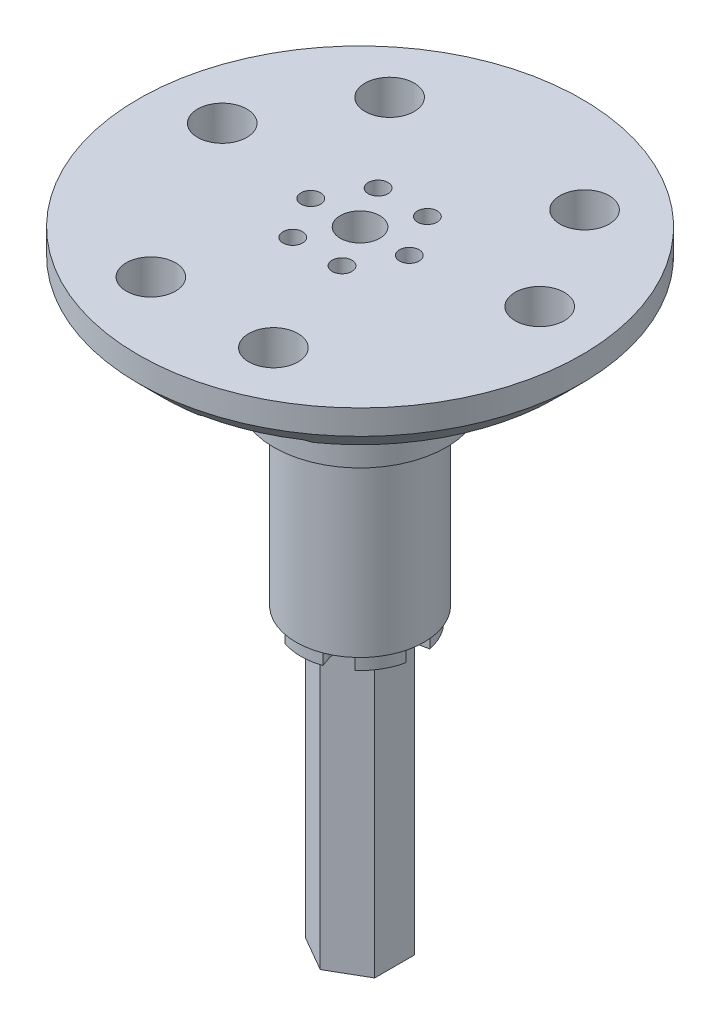
SolidWorks part; units mm, degrees
material "ABS"
ref_plane "Front Plane" through (0, 0, 0) normal (0, 0, 1) x (1, 0, 0)
ref_plane "Top Plane" through (0, 0, 0) normal (0, 1, 0) x (1, 0, 0)
ref_plane "Right Plane" through (0, 0, 0) normal (1, 0, 0) x (0, 0, -1)
sketch "Sketch1" plane through (0, 0, 0) normal (0, 0, 1) x (1, 0, 0)
  line L0 (1.5564, -6.25) -> (1.5564, 63.25)
  line L1 (9.5564, -6.25) -> (9.5564, -3.25)
  line L2 (4.5564, -6.25) -> (1.5564, -6.25)
  line L5 (-2.4436, 63.25) -> (-2.4436, -63.25) construction
  line L11 (42.5564, 63.25) -> (42.5564, 53.25)
  line L15 (42.5564, 53.25) -> (22.5564, 53.25)
  line L16 (1.5564, 63.25) -> (42.5564, 63.25)
  line L20 (17.5564, 48.25) -> (17.5564, 40.25)
  line L21 (15.5564, 41.25) -> (15.5564, 40.25)
  line L22 (16.0564, 41.25) -> (15.5564, 41.25)
  line L23 (15.0564, 42.25) -> (15.0564, 33.25)
  line L24 (15.0564, 33.25) -> (12.5564, 33.25)
  line L25 (10.5564, 31.25) -> (10.5564, -3.25)
  line L36 (9.5564, -6.25) -> (4.5564, -6.25)
  line L40 (15.5564, 40.25) -> (17.5564, 40.25)
  line L42 (10.5564, -3.25) -> (9.5564, -3.25)
  arc A1 (22.5564, 53.25) -> (17.5564, 48.25) centre (22.5564, 48.25) ccw
  arc A2 (16.0564, 41.25) -> (15.0564, 42.25) centre (16.0564, 42.25) ccw
  arc A3 (12.5564, 33.25) -> (10.5564, 31.25) centre (12.5564, 31.25) ccw
revolve "Revolve1" add sketch "Sketch1" angle 360 about L5
sketch "Sketch2" plane through (0, -6.25, 0) normal (0, -1, 0) x (1, 0, 0)
  line L0 (4.5564, 4.0415) -> (4.5564, -4.0415)
  line L1 (-2.4436, 8.0829) -> (4.5564, 4.0415)
  line L2 (-9.4436, 4.0415) -> (-2.4436, 8.0829)
  line L3 (-9.4436, -4.0415) -> (-9.4436, 4.0415)
  line L4 (-2.4436, -8.0829) -> (-9.4436, -4.0415)
  line L5 (4.5564, -4.0415) -> (-2.4436, -8.0829)
  line L6 (-2.4436, 12) -> (-2.4436, -12) construction
  circle A0 centre (-2.4436, 0) radius 4
  circle A1 centre (-2.4436, 0) radius 12 construction
  circle A2 centre (-2.4436, 0) radius 12 construction
extrude "Boss-Extrude1" add sketch "Sketch2" along normal blind 57
sketch "Sketch3" plane through (0, -6.25, 0) normal (0, -1, 0) x (1, 0, 0)
  line L0 (-2.4436, 12) -> (-2.4436, -12) construction
  line L1 (-9.067, 7.4921) -> (-10.3917, 8.9905)
  line L2 (-5.6203, 9.482) -> (-6.2556, 11.3784)
  line L3 (4.1797, 7.4921) -> (5.5044, 8.9905)
  line L4 (0.733, 9.482) -> (1.3683, 11.3784)
  line L5 (7.3564, -1.99) -> (9.3164, -2.388)
  line L6 (7.3564, 1.99) -> (9.3164, 2.388)
  line L7 (0.733, -9.482) -> (1.3683, -11.3784)
  line L8 (4.1797, -7.4921) -> (5.5044, -8.9905)
  line L9 (-9.067, -7.4921) -> (-10.3917, -8.9905)
  line L10 (-5.6203, -9.482) -> (-6.2556, -11.3784)
  line L11 (-12.2436, 1.99) -> (-14.2036, 2.388)
  line L12 (-12.2436, -1.99) -> (-14.2036, -2.388)
  arc A1 (0.733, 9.482) -> (4.1797, 7.4921) centre (2.5564, 8.6603) ccw
  arc A2 (-12.2436, -1.99) -> (-12.2436, 1.99) centre (-12.4436, 0) ccw
  arc A3 (4.1797, -7.4921) -> (0.733, -9.482) centre (2.5564, -8.6603) ccw
  arc A4 (-9.067, 7.4921) -> (-5.6203, 9.482) centre (-7.4436, 8.6603) ccw
  arc A5 (-5.6203, -9.482) -> (-9.067, -7.4921) centre (-7.4436, -8.6603) ccw
  arc A6 (7.3564, 1.99) -> (7.3564, -1.99) centre (7.5564, 0) ccw
  circle A8 centre (-2.4436, 0) radius 12 construction
  circle A9 centre (-2.4436, 0) radius 12 construction
  arc A11 (-6.2556, 11.3784) -> (-10.3917, 8.9905) centre (-2.4436, 0) ccw
  arc A12 (-10.3917, -8.9905) -> (-6.2556, -11.3784) centre (-2.4436, 0) ccw
  arc A13 (-14.2036, 2.388) -> (-14.2036, -2.388) centre (-2.4436, 0) ccw
  arc A14 (1.3683, -11.3784) -> (5.5044, -8.9905) centre (-2.4436, 0) ccw
  arc A15 (9.3164, -2.388) -> (9.3164, 2.388) centre (-2.4436, 0) ccw
  arc A16 (5.5044, 8.9905) -> (1.3683, 11.3784) centre (-2.4436, 0) ccw
  arc A17 (5.5044, 8.9905) -> (1.3683, 11.3784) centre (-2.4436, 0) ccw
  arc A18 (-6.2556, 11.3784) -> (-10.3917, 8.9905) centre (-2.4436, 0) ccw
  arc A19 (-14.2036, 2.388) -> (-14.2036, -2.388) centre (-2.4436, 0) ccw
  arc A20 (-10.3917, -8.9905) -> (-6.2556, -11.3784) centre (-2.4436, 0) ccw
  arc A21 (1.3683, -11.3784) -> (5.5044, -8.9905) centre (-2.4436, 0) ccw
  arc A22 (9.3164, -2.388) -> (9.3164, 2.388) centre (-2.4436, 0) ccw
  point P53 (-2.4436, 0)
  circle M3 centre (-2.4436, 0) radius 12
  dimension "D1" = 6
extrude "Cut-Extrude6" cut sketch "Sketch3" against normal blind 3 contours L4 A1 L3 M3 | L1 A4 L2 M3 | L12 A2 L11 M3 | L6 A6 L5 M3 | L8 A3 L7 M3 | L10 A5 L9 M3 region at (-7.5487, -6.25, 8.8422) region at (-12.6537, -6.25, 0) region at (2.6614, -6.25, 8.8422) region at (-7.5487, -6.25, -8.8422) region at (7.7664, -6.25, 0) region at (2.6614, -6.25, -8.8422)
sketch "Sketch4" plane through (0, -3.25, 0) normal (0, -1, 0) x (1, 0, 0)
  line L0 (-2.4436, 12) -> (-2.4436, -12) construction
  circle A1 centre (2.5564, 8.6603) radius 2
  circle A2 centre (-12.4436, 0) radius 2
  circle A3 centre (2.5564, -8.6603) radius 2
  circle A4 centre (-7.4436, 8.6603) radius 2
  circle A5 centre (-7.4436, -8.6603) radius 2
  circle A6 centre (7.5564, 0) radius 2
  arc A8 (1.3683, 11.3784) -> (-6.2556, 11.3784) centre (-2.4436, 0) ccw construction
  arc A9 (-6.2556, -11.3784) -> (1.3683, -11.3784) centre (-2.4436, 0) ccw construction
extrude "Cut-Extrude7" cut sketch "Sketch4" against normal through all
sketch "Sketch5" plane through (0, 63.25, 0) normal (0, 1, 0) x (1, 0, 0)
  line L6 (-2.4436, -45) -> (-2.4436, 45) construction
  circle A2 centre (9.9936, -30.0261) radius 5
  circle A3 centre (29.7783, 4.2421) radius 5
  circle A4 centre (17.3411, 25.784) radius 5
  circle A5 centre (-22.2284, 25.784) radius 5
  circle A6 centre (-34.6656, 4.2421) radius 5
  circle A7 centre (-14.8808, -30.0261) radius 5
  circle A23 centre (-2.4436, 0) radius 45 construction
extrude "Cut-Extrude8" cut sketch "Sketch5" against normal up to next
sketch "Sketch6" plane through (0, 53.25, 0) normal (0, -1, 0) x (1, 0, 0)
  circle A17 centre (29.7783, -4.2421) radius 11
  circle A18 centre (17.3411, -25.784) radius 11
  circle A19 centre (9.9936, 30.0261) radius 11
  circle A20 centre (-14.8808, 30.0261) radius 11
  circle A21 centre (-34.6656, -4.2421) radius 11
  circle A22 centre (-22.2284, -25.784) radius 11
extrude "Cut-Extrude9" cut sketch "Sketch6" against normal blind 1 and the other way blind 11
chamfer "Sfazowanie1" distance 5 angle 45 1 edges at (-2.4436, 53.25, 45)
